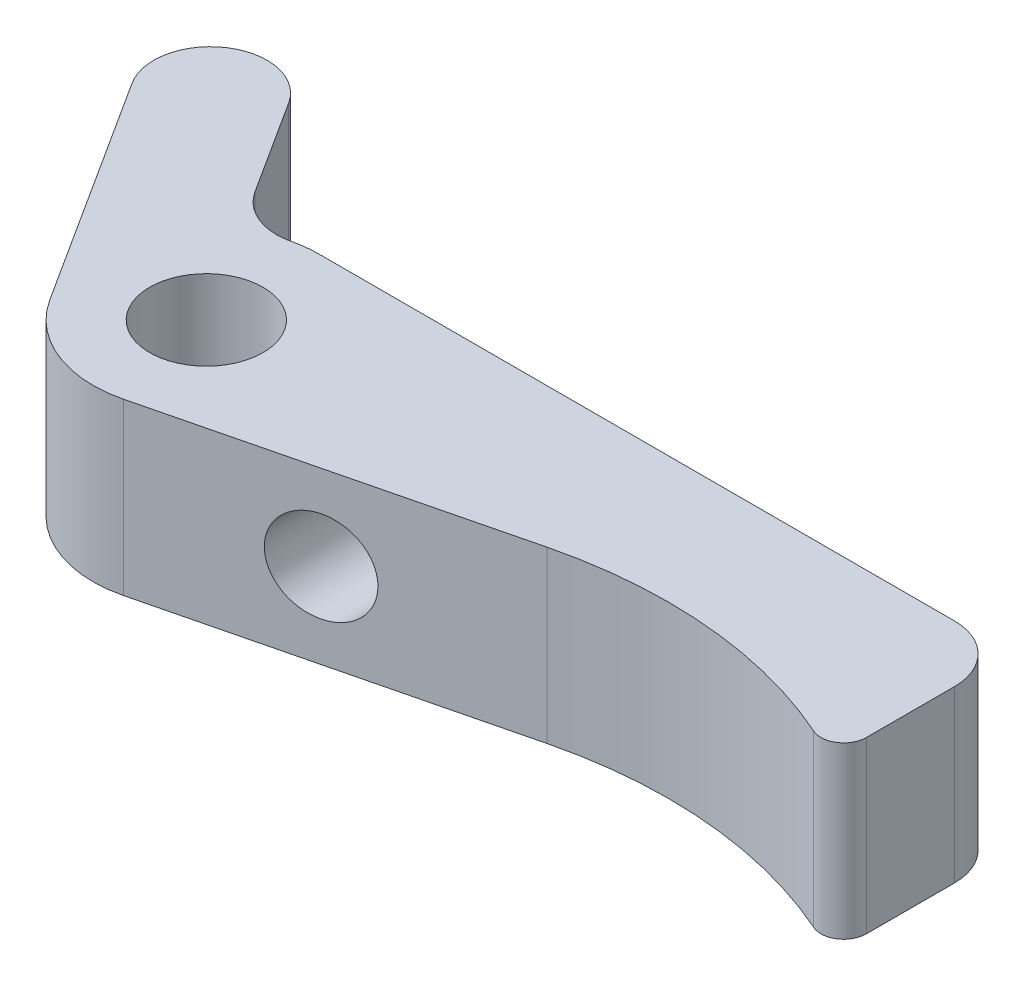
SolidWorks part; units mm, degrees
material "6061-T6 (SS)"
ref_plane "Front" through (0, 0, 0) normal (0, 0, 1) x (1, 0, 0)
ref_plane "Top" through (0, 0, 0) normal (0, 1, 0) x (1, 0, 0)
ref_plane "Right" through (0, 0, 0) normal (1, 0, 0) x (0, 0, -1)
sketch "Sketch1" plane through (0, 0, 0) normal (0, 1, 0) x (1, 0, 0)
  line L0 (0, 6.35) -> (38.735, 6.35)
  line L1 (38.735, 6.35) -> (38.735, -3.81)
  line L2 (1.5172, -6.1661) -> (20.5672, -1.4788)
  line L3 (-3.4246, 5.3474) -> (-9.9315, 15.5074)
  line L4 (-9.9315, 15.5074) -> (-15.2788, 12.0827)
  line L5 (-15.2788, 12.0827) -> (-5.3474, -3.4246)
  circle A0 centre (0, 0) radius 3.175
  circle A1 centre (0, 0) radius 6.35
  arc A2 (20.5672, -1.4788) -> (38.735, -3.81) centre (26.6359, -26.1432) cw
  point P12 (28.5942, -3.4246)
  point P13 (19.4248, -1.3529)
  point P16 (20.9019, -0.5432)
  point P17 (2.8602, -5.6694)
  point P18 (21.8484, 0)
  dimension "D1" = 6.35
  dimension "D2" = 12.7
  dimension "D5" = 19.05
  dimension "D7" = 12.065
  dimension "D6" = 25.4
  dimension "D3" = 38.735
  dimension "D4" = 10.16
  dimension "D8" = 6.35
  dimension "D9" = 10.16
extrude "Boss-Extrude1" add sketch "Sketch1" along normal blind 9.525 contours A1 A0 | L2 A2 L1 L0 A1 | A1 L3 L4 L5 region at (20.9795, 0, -1.9449) region at (4.3631, 0, -4.3631) region at (-9.094, 0, -7.9821)
fillet "Fillet1" radius 3.175 4 edges at (38.735, 4.7625, -6.35) (-3.4246, 4.7625, -5.3474) (-15.2788, 4.7625, -12.0827) (-9.9315, 4.7625, -15.5074)
fillet "Fillet2" radius 1.27 1 edges at (38.735, 4.7625, 3.81)
ref_plane "Plane2" through (0, 0, 6.35) normal (0, 0, 1) x (1, 0, 0)
sketch "Sketch6" plane through (0, 0, 6.35) normal (0, 0, 1) x (1, 0, 0)
  line L2 (10.4072, 9.525) -> (10.4072, 0)
  line L4 (1.5172, 9.525) -> (20.5672, 9.525) construction
  line L5 (1.5172, 0) -> (20.5672, 0) construction
  line L6 (1.5172, 9.525) -> (1.5172, 0) construction
  point P0 (10.4072, 4.7625)
  dimension "D1" = 8.89
hole_wizard "1/4-20 Tapped Hole1" positions "Sketch6" profile "Sketch5" tap size "1/4-20" standard "ANSI Inch"
sketch "Sketch5" plane through (10.4072, 4.7625, 6.35) normal (1, 0, 0) x (0, -1, 0)
  line L0 (0, 0) -> (0, 10.4238)
  line L1 (0, 10.4238) -> (2.5527, 8.89)
  line L2 (2.5527, 8.89) -> (2.5527, 0)
  line L5 (2.5527, 0) -> (0, 0)
  line L10 (0, 10.4238) -> (-2.5527, 8.89) construction
  line L11 (0, -6.35) -> (0, 107.95) construction
  dimension "Tap Drill Dia." = 5.1054
  dimension "Tap Drill Depth" = 8.89
  dimension "Drill Angle" = 118
cosmetic thread "Hole Thread1" parameters "D1"=12.7, "D2"=6.35
